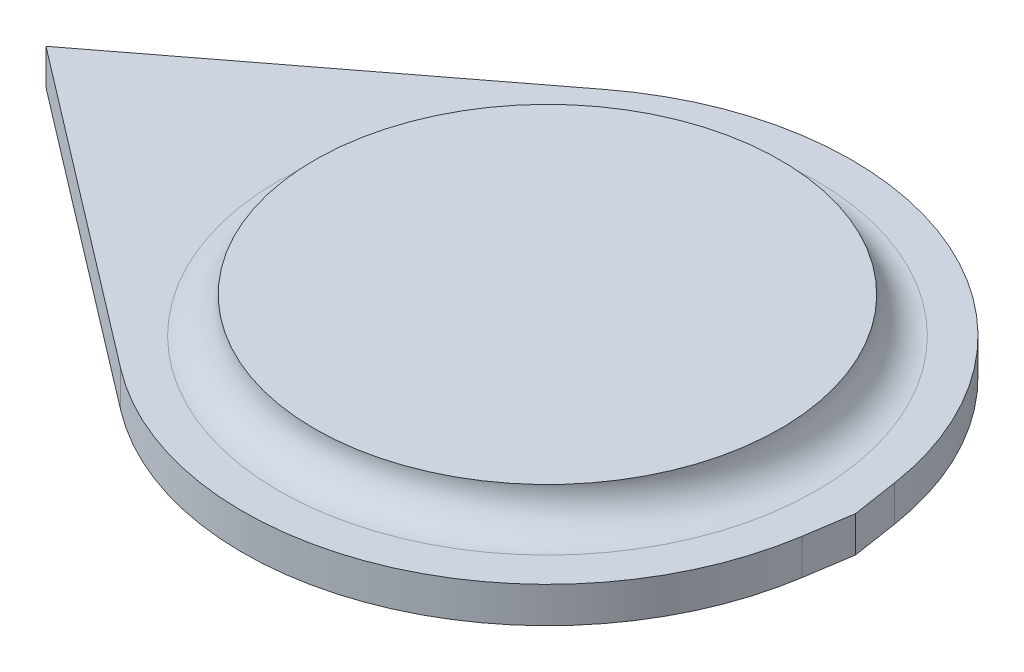
SolidWorks part; units mm, degrees
ref_plane "Front Plane" through (0, 0, 0) normal (0, 0, 1) x (1, 0, 0)
ref_plane "Top Plane" through (0, 0, 0) normal (0, 1, 0) x (1, 0, 0)
ref_plane "Right Plane" through (0, 0, 0) normal (1, 0, 0) x (0, 0, -1)
sketch "Sketch1" plane through (0, 0, 0) normal (0, 1, 0) x (1, 0, 0)
  line L0 (-25.8036, 33.7702) -> (-70, 0)
  line L3 (-70, 0) -> (-25.8036, -33.7702)
  line L4 (42.0058, 6.4623) -> (43, 0)
  line L5 (43, 0) -> (42.0058, -6.4623)
  circle A0 centre (0, 0) radius 32.5
  arc A1 (-25.8036, -33.7702) -> (42.0058, -6.4623) centre (0, 0) ccw
  arc A4 (42.0058, 6.4623) -> (-25.8036, 33.7702) centre (0, 0) ccw
  point P6 (0, 0)
  point P9 (39.523, 15.6263)
  point P10 (39.9276, -14.5615)
  dimension "D1" = 65
  dimension "D2" = 70
  dimension "D3" = 10
  dimension "D4" = 43
extrude "Boss-Extrude1" add sketch "Sketch1" along normal blind 5 contours A1 L5 L4 A4 L0 L3
sketch "Sketch2" plane through (0, 5, 0) normal (0, 1, 0) x (1, 0, 0)
  circle A0 centre (0, 0) radius 32.5
  dimension "D1" = 65
extrude "Boss-Extrude2" add sketch "Sketch2" along normal blind 5
fillet "Fillet1" radius 5 1 edges at (0, 5, 32.5)
